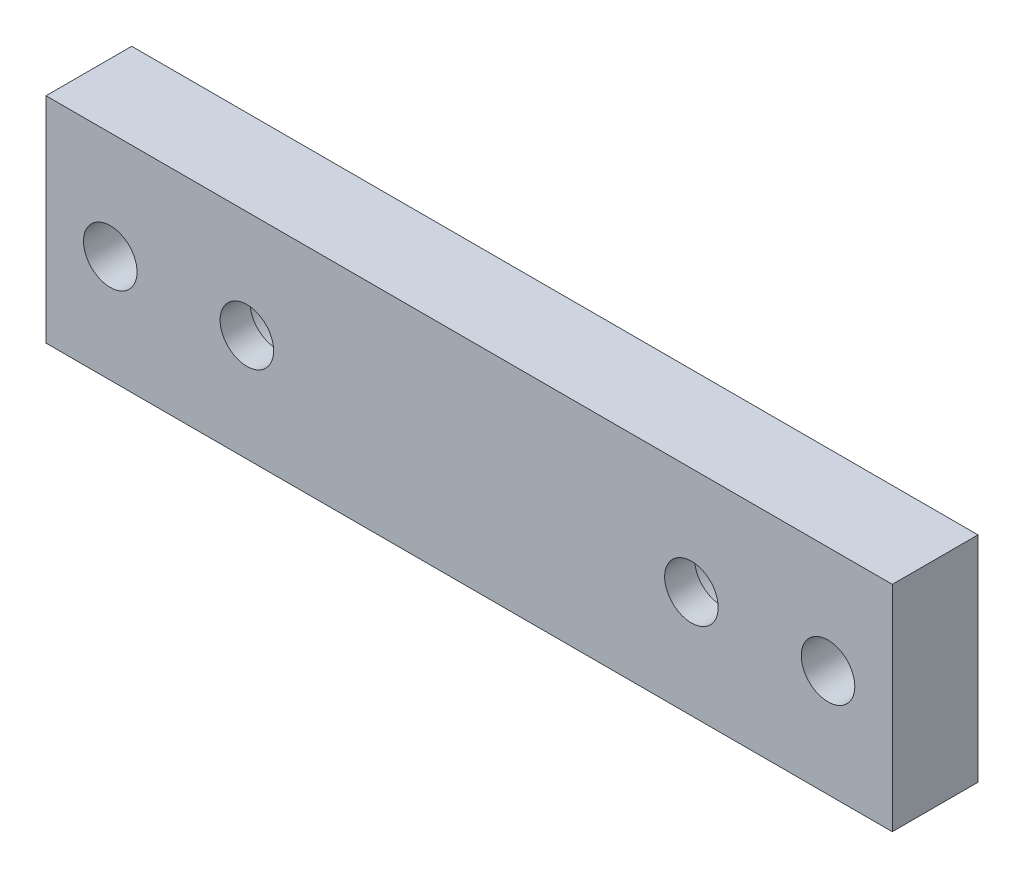
SolidWorks part; units mm, degrees
ref_plane "前视基准面" through (0, 0, 0) normal (0, 0, 1) x (1, 0, 0)
ref_plane "上视基准面" through (0, 0, 0) normal (0, 1, 0) x (1, 0, 0)
ref_plane "右视基准面" through (0, 0, 0) normal (1, 0, 0) x (0, 0, -1)
sketch "草图1" plane through (0, 0, 0) normal (0, 0, 1) x (1, 0, 0)
  line L0 (-40.7377, 36.5405) -> (0.7623, 36.5405)
  line L1 (-59.4877, 46.5405) -> (19.5123, 46.5405)
  line L2 (-59.4877, 46.5405) -> (-59.4877, 26.5405)
  line L3 (-59.4877, 26.5405) -> (19.5123, 26.5405)
  line L4 (19.5123, 46.5405) -> (19.5123, 26.5405)
  line L5 (-59.4877, 46.5405) -> (19.5123, 26.5405) construction
  line L6 (-59.4877, 26.5405) -> (19.5123, 46.5405) construction
  line L7 (-59.4877, 46.5405) -> (-47.4877, 46.5405)
  line L8 (-47.4877, 46.5405) -> (-47.4877, 26.5405) construction
  line L9 (-47.4877, 26.5405) -> (-59.4877, 46.5405) construction
  line L10 (-59.4877, 26.5405) -> (-47.4877, 46.5405) construction
  line L11 (7.5123, 46.5405) -> (7.5123, 26.5405) construction
  line L12 (7.5123, 26.5405) -> (19.5123, 26.5405) construction
  line L13 (7.5123, 46.5405) -> (19.5123, 26.5405) construction
  line L14 (19.5123, 46.5405) -> (7.5123, 26.5405) construction
  circle A0 centre (-40.7377, 36.5405) radius 2.5
  circle A1 centre (0.7623, 36.5405) radius 2.5
  circle A2 centre (-40.7377, 36.5405) radius 4.5
  circle A3 centre (0.7623, 36.5405) radius 4.5
  circle A4 centre (-53.4877, 36.5405) radius 2.5
  circle A5 centre (13.5123, 36.5405) radius 2.5
  point P0 (-19.9877, 36.5405)
  point P8 (-19.9877, 36.5405)
  point P16 (7.5123, 46.5405)
  dimension "D4" = 12
  dimension "D5" = 12
  dimension "D1" = 79
  dimension "D2" = 20
  dimension "D3" = 41.5
extrude "凸台-拉伸1" add sketch "草图1" along normal blind 8 contours L4 L1 L2 L3 A5 A4 A3 A2 | A3 A1 | A2 A0 region at (-45.1104, 36.5405, 0) region at (0.7623, 40.9132, 0) region at (-53.4877, 45.7256, 0)
extrude "切除-拉伸1" cut sketch "草图1<3>" along normal blind 5.2 contours A3
sketch "草图1<3>" plane through (0, 0, 0) normal (0, 0, 1) x (1, 0, 0) same geometry as "草图1"
extrude "切除-拉伸2" cut sketch "草图1<4>" along normal blind 5.2 contours A2
sketch "草图1<4>" plane through (0, 0, 0) normal (0, 0, 1) x (1, 0, 0) same geometry as "草图1"
